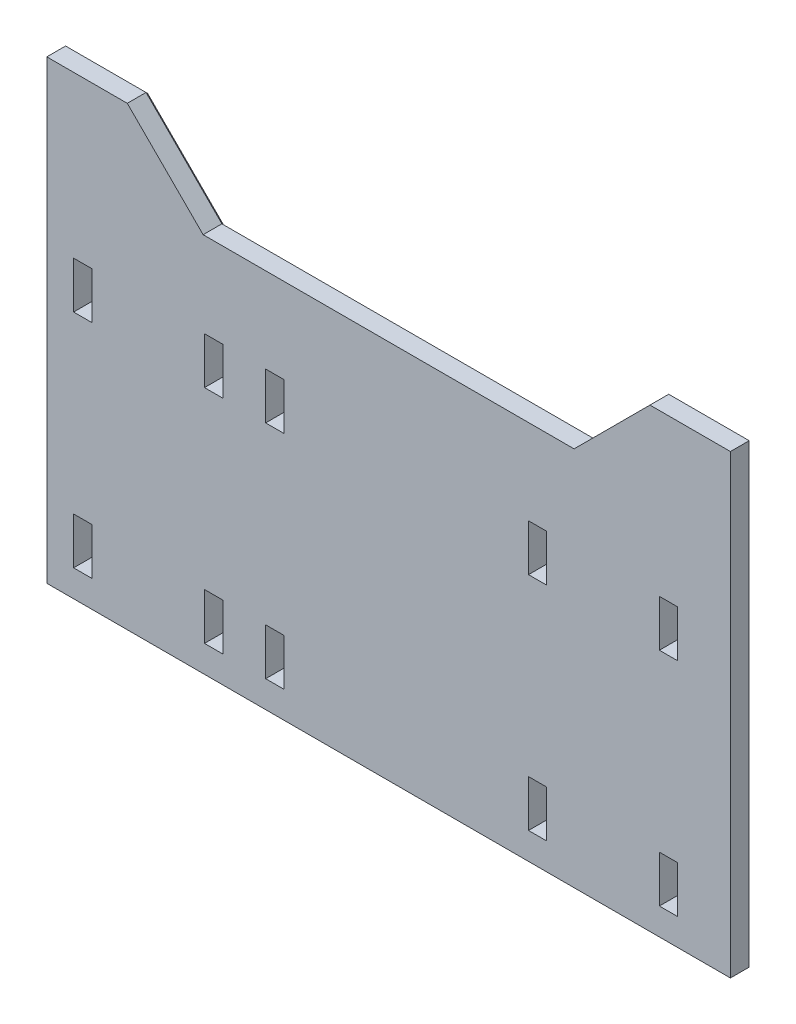
SolidWorks part; units mm, degrees
ref_plane "Front Plane" through (0, 0, 0) normal (0, 0, 1) x (1, 0, 0)
ref_plane "Top Plane" through (0, 0, 0) normal (0, 1, 0) x (1, 0, 0)
ref_plane "Right Plane" through (0, 0, 0) normal (1, 0, 0) x (0, 0, -1)
sketch "Sketch1" plane through (0, 0, 0) normal (0, 0, 1) x (1, 0, 0)
  line L6 (-34.3201, 25) -> (-30.9201, 25)
  line L7 (26.0799, 25) -> (29.4799, 25)
  line L8 (26.0799, 25) -> (26.0799, 16.3)
  line L9 (26.0799, 16.3) -> (29.4799, 16.3)
  line L10 (29.4799, 25) -> (29.4799, 16.3)
  line L12 (26.0799, -16.3) -> (29.4799, -16.3)
  line L13 (26.0799, -25) -> (26.0799, -16.3)
  line L14 (29.4799, -25) -> (29.4799, -16.3)
  line L15 (26.0799, -25) -> (29.4799, -25)
  line L16 (-19.5201, 25) -> (-22.9201, 25)
  line L17 (-19.5201, 25) -> (-19.5201, 16.3)
  line L18 (-22.9201, 25) -> (-22.9201, 16.3)
  line L19 (-19.5201, 16.3) -> (-22.9201, 16.3)
  line L20 (-19.5201, -16.3) -> (-22.9201, -16.3)
  line L21 (-19.5201, -25) -> (-19.5201, -16.3)
  line L22 (-22.9201, -25) -> (-22.9201, -16.3)
  line L23 (-19.5201, -25) -> (-22.9201, -25)
  line L39 (50.4799, 25) -> (53.8799, 25)
  line L40 (50.4799, 25) -> (50.4799, 16.3)
  line L41 (50.4799, 16.3) -> (53.8799, 16.3)
  line L42 (53.8799, 25) -> (53.8799, 16.3)
  line L43 (50.4799, -16.3) -> (53.8799, -16.3)
  line L44 (50.4799, -16.3) -> (50.4799, -25)
  line L45 (50.4799, -25) -> (53.8799, -25)
  line L46 (53.8799, -16.3) -> (53.8799, -25)
  line L47 (-34.3201, 25) -> (-34.3201, 16.3)
  line L48 (-34.3201, 16.3) -> (-30.9201, 16.3)
  line L49 (-30.9201, 25) -> (-30.9201, 16.3)
  line L50 (-34.3201, -16.3) -> (-30.9201, -16.3)
  line L51 (-34.3201, -16.3) -> (-34.3201, -25)
  line L52 (-34.3201, -25) -> (-30.9201, -25)
  line L53 (-30.9201, -16.3) -> (-30.9201, -25)
  line L60 (-58.7201, 25) -> (-55.3201, 25)
  line L61 (-58.7201, 25) -> (-58.7201, 16.3)
  line L62 (-58.7201, 16.3) -> (-55.3201, 16.3)
  line L63 (-55.3201, 25) -> (-55.3201, 16.3)
  line L64 (-58.7201, -16.3) -> (-55.3201, -16.3)
  line L65 (-58.7201, -16.3) -> (-58.7201, -25)
  line L66 (-58.7201, -25) -> (-55.3201, -25)
  line L67 (-55.3201, -16.3) -> (-55.3201, -25)
  line L80 (-63.7201, 30) -> (63.7201, 30)
  line L81 (63.7201, 30) -> (63.7201, -30)
  line L82 (52.1799, 25) -> (52.1799, 16.3) construction
  line L83 (27.7799, 16.3) -> (27.7799, 25) construction
  line L84 (-63.7201, 30) -> (-63.7201, -30)
  line L85 (-63.7201, -30) -> (63.7201, -30)
  line L87 (53.2799, 20.65) -> (50.4799, 20.65) construction
  line L88 (29.4799, 20.65) -> (26.0799, 20.65) construction
  line L89 (53.8799, -20.65) -> (50.4799, -20.65) construction
  line L90 (52.1799, -16.3) -> (52.1799, -25) construction
  line L91 (27.7799, -16.3) -> (27.7799, -25) construction
  line L92 (29.4799, -20.65) -> (26.0799, -20.65) construction
  line L93 (-19.5201, -20.65) -> (-22.9201, -20.65) construction
  line L94 (-21.2201, -16.3) -> (-21.2201, -25) construction
  line L95 (-32.6201, -16.3) -> (-32.6201, -25) construction
  line L96 (-30.9201, -20.65) -> (-34.3201, -20.65) construction
  line L97 (-55.3201, -20.65) -> (-58.7201, -20.65) construction
  line L98 (-57.0201, -16.3) -> (-57.0201, -25) construction
  line L99 (-57.0201, 25) -> (-57.0201, 16.3) construction
  line L100 (-32.6201, 25) -> (-32.6201, 16.3) construction
  line L101 (-21.2201, 25) -> (-21.2201, 16.3) construction
  line L102 (-55.3201, 20.65) -> (-58.7201, 20.65) construction
  line L103 (-34.3201, 20.65) -> (-30.9201, 20.65) construction
  line L104 (-19.5201, 20.65) -> (-22.9201, 20.65) construction
  point P0 (0, 0)
  point P86 (0, 30)
  point P87 (63.7201, 0)
  dimension "D1" = 8.7
  dimension "D2" = 3.4
  dimension "D3" = 127.4402
  dimension "D4" = 60
  dimension "D7" = 11.4
  dimension "D8" = 24.4
  dimension "D5" = 27.7799
  dimension "D6" = 21.2201
  dimension "D10" = 20.65
  dimension "D11" = 20.65
  dimension "D9" = 24.4
extrude "Boss-Extrude1" add sketch "Sketch1" against normal blind 4
sketch "Sketch2" plane through (0, 0, 0) normal (0, 0, 1) x (1, 0, 0)
  line L0 (-63.7201, 30) -> (-63.7201, 55)
  line L1 (-63.7201, 55) -> (-48.7201, 55)
  line L2 (-48.7201, 55) -> (-34.578, 40.8579)
  line L7 (63.7201, 30) -> (-63.7201, 30)
  line L8 (48.7201, 55) -> (63.7201, 55)
  line L9 (63.7201, 55) -> (63.7201, 30)
  line L10 (48.7201, 55) -> (34.578, 40.8579)
  line L11 (34.578, 40.8579) -> (-34.578, 40.8579)
  line L12 (-63.7201, 30) -> (-63.7201, -30) construction
  line L14 (63.7201, -30) -> (63.7201, 30) construction
  dimension "D1" = 25
  dimension "D2" = 15
  dimension "D3" = 135
  dimension "D4" = 20
extrude "Boss-Extrude2" add sketch "Sketch2" against normal blind 4
chamfer "Chamfer1" distance 0.5 angle 45 48 edges at (56.2201, 55, -4) (41.649, 47.9289, -4) (0, 40.8579, -4) (-41.649, 47.9289, -4) (-56.2201, 55, -4) (-63.7201, 12.5, -4) (0, -30, -4) (63.7201, 12.5, -4) (29.4799, 20.65, -4) (27.7799, 16.3, -4) (26.0799, 20.65, -4) (27.7799, 25, -4) (29.4799, -20.65, -4) (27.7799, -25, -4) (26.0799, -20.65, -4) (27.7799, -16.3, -4) (-22.9201, 20.65, -4) (-21.2201, 25, -4) (-19.5201, 20.65, -4) (-21.2201, 16.3, -4) (-22.9201, -20.65, -4) (-21.2201, -16.3, -4) (-19.5201, -20.65, -4) (-21.2201, -25, -4) (-30.9201, 20.65, -4) (-32.6201, 16.3, -4) (-34.3201, 20.65, -4) (-32.6201, 25, -4) (-30.9201, -20.65, -4) (-32.6201, -25, -4) (-34.3201, -20.65, -4) (-32.6201, -16.3, -4) (53.8799, 20.65, -4) (52.1799, 16.3, -4) (50.4799, 20.65, -4) (52.1799, 25, -4) (53.8799, -20.65, -4) (52.1799, -25, -4) (50.4799, -20.65, -4) (52.1799, -16.3, -4) (-55.3201, 20.65, -4) (-57.0201, 16.3, -4) (-58.7201, 20.65, -4) (-57.0201, 25, -4) (-55.3201, -20.65, -4) (-57.0201, -25, -4) (-58.7201, -20.65, -4) (-57.0201, -16.3, -4)
equation "\"pin_hole_height\"=8.7"
equation "\"D1@Sketch1\"=\"pin_hole_height\""
equation "\"pin_hole_width\"=3.4"
equation "\"D2@Sketch1\"=\"pin_hole_width\""
